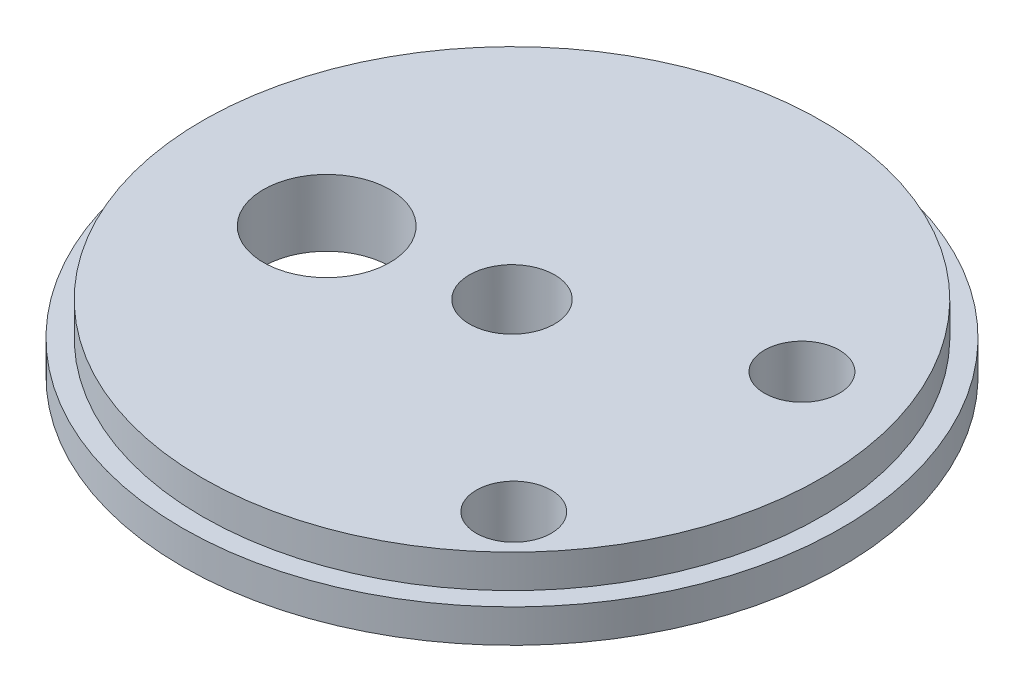
SolidWorks part; units mm, degrees
ref_plane "Front Plane" through (0, 0, 0) normal (0, 0, 1) x (1, 0, 0)
ref_plane "Top Plane" through (0, 0, 0) normal (0, 1, 0) x (1, 0, 0)
ref_plane "Right Plane" through (0, 0, 0) normal (1, 0, 0) x (0, 0, -1)
sketch "Sketch1" plane through (0, 0, 0) normal (0, 1, 0) x (1, 0, 0)
  circle A0 centre (0, 0) radius 25.146
  dimension "D1" = 50.292
extrude "Boss-Extrude1" add sketch "Sketch1" along normal blind 2.54
sketch "Sketch2" plane through (0, 2.54, 0) normal (0, 1, 0) x (1, 0, 0)
  circle A0 centre (0, 0) radius 23.622
  dimension "D1" = 47.244
extrude "Boss-Extrude2" add sketch "Sketch2" along normal blind 2.54
sketch "Sketch3" plane through (0, 0, 0) normal (0, -1, 0) x (1, 0, 0)
  circle A0 centre (0, 0) radius 3.2512
  circle A1 centre (-11.9211, 2.2188) radius 4.826
  dimension "D1" = 6.5024
  dimension "D2" = 9.652
extrude "Cut-Extrude1" cut sketch "Sketch3" against normal through all and the other way through all
sketch "Sketch4" plane through (0, 0, 0) normal (0, -1, 0) x (1, 0, 0)
  line L0 (15.8367, -6.2866) -> (14.0961, 13.9587) construction
  line L1 (11.6256, -9.198) -> (11.1197, -3.3137) construction
  line L2 (0, 0) -> (15.184, 1.3054) construction
  circle A0 centre (15.8367, -6.2866) radius 2.8575
  circle A1 centre (14.0961, 13.9587) radius 2.8575
  dimension "D1" = 5.715
  dimension "D2" = 15.24
  dimension "D3" = 7.62
  dimension "D4" = 12.7
extrude "Cut-Extrude2" cut sketch "Sketch4" against normal up to surface (5.08 mm away) up to face at (0, 5.08, -3.2512)
